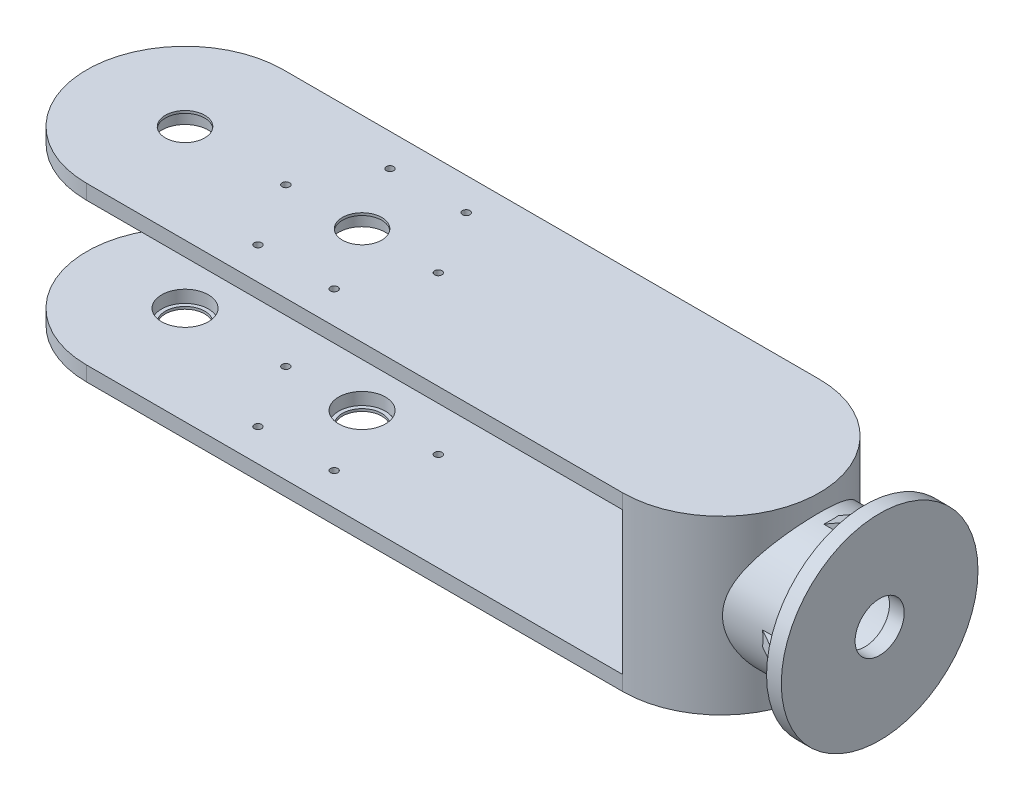
SolidWorks part; units mm, degrees
ref_plane "前视基准面" through (0, 0, 0) normal (0, 0, 1) x (1, 0, 0)
ref_plane "上视基准面" through (0, 0, 0) normal (0, 1, 0) x (1, 0, 0)
ref_plane "右视基准面" through (0, 0, 0) normal (1, 0, 0) x (0, 0, -1)
sketch "草图1" plane through (0, 0, 0) normal (0, 1, 0) x (1, 0, 0)
  line L1 (0, 40) -> (218, 40)
  line L4 (218, -40) -> (0, -40)
  arc A0 (0, 40) -> (0, -40) centre (0, 0) ccw
  arc A1 (218, -40) -> (218, 40) centre (218, 0) ccw
  dimension "D1" = 80
  dimension "D2" = 218
  dimension "D4" = 40
extrude "拉伸1" add sketch "草图1" along normal blind 3 and the other way blind 3
sketch "草图2" plane through (0, 3, 0) normal (0, 1, 0) x (-1, 0, 0)
  line L0 (-218, -31.8673) -> (-218, -40)
  line L1 (-218, 31.8673) -> (-218, 40)
  arc A0 (-218, 40) -> (-218, -40) centre (-218, 0) ccw
  arc A1 (-218, 31.8673) -> (-218, -31.8673) centre (-218, 0) ccw
extrude "拉伸2" add sketch "草图2" along normal blind 58
ref_plane "基准面1" through (282.5, 0, 0) normal (1, 0, 0) x (0, 0, -1)
sketch "草图3" plane through (282.5, 0, 0) normal (1, 0, 0) x (0, 0, -1)
  circle A0 centre (0, 32) radius 40
extrude "拉伸3" add sketch "草图3" along normal blind 0.0001 and the other way blind 6 separate body
sketch "草图4" plane through (0, 0, 0) normal (0, 0, 1) x (1, 0, 0)
  line L0 (282.5, 76.1494) -> (282.5, -15.8787)
  line L1 (282.5, -44) -> (282.5, 44) construction
  line L2 (282.5, -15.8787) -> (330.2143, 15.8142)
extrude "切除-拉伸1" cut sketch "草图4" against normal through all and the other way through all
sketch "草图5" plane through (276.5, 0, 0) normal (-1, 0, 0) x (0, 0, 1)
  circle A0 centre (0, 32) radius 28
  circle A1 centre (0, 32) radius 24
extrude "拉伸4" add sketch "草图5" along normal up to surface (29.9343 mm away) up to face at (231.3333, 20.3333, 0)
sketch "草图9" plane through (0, 0, 0) normal (0, 0, 1) x (1, 0, 0)
  line L0 (276.5, -3.6675) -> (263.0188, 4)
  line L1 (276.5, 72) -> (276.5, -8) construction
  line L2 (258, 4) -> (276.5, 4) construction
rib "筋5" sketch "草图9" sketch "草图9" thickness 6 extrusion direction parallel to sketch draft on no parameters "D1"=6
ref_axis "基准轴1" through (276.5, 32, 0) along (-1, 0, 0)
pattern_circular "阵列(圆周)1" count 4 every 90 about axis through (276.5, 32, 0) along (-1, 0, 0) of "筋5"
ref_plane "基准面2" through (0, 32, 0) normal (0, 1, 0) x (-1, 0, 0)
mirror "镜向1" about plane through (0, 32, 0) normal (0, 1, 0) of "拉伸1"
sketch "草图10" plane through (282.5, 0, 0) normal (1, 0, 0) x (0, 0, -1)
  line L0 (44, 32) -> (-44, 32) construction
  circle A0 centre (0, 32) radius 10
extrude "切除-拉伸2" cut sketch "草图10" against normal through all
sketch "草图11" plane through (0, 67, 0) normal (0, 1, 0) x (-1, 0, 0)
  circle A0 centre (0, 0) radius 8
extrude "切除-拉伸3" cut sketch "草图11" against normal through all
sketch "草图12" plane through (0, 67, 0) normal (0, 1, 0) x (-1, 0, 0)
  circle A0 centre (-72, 0) radius 8
  dimension "D1" = 72
extrude "切除-拉伸4" cut sketch "草图12" against normal through all
sketch "草图13" plane through (0, 3, 0) normal (0, 1, 0) x (-1, 0, 0)
  circle A0 centre (-72, 0) radius 9.5
  circle A1 centre (0, 0) radius 9.5
  dimension "D1" = 19
extrude "切除-拉伸5" cut sketch "草图13" against normal blind 5
mirror "镜向2" about plane through (0, 32, 0) normal (0, 1, 0) of "切除-拉伸5"
sketch "草图14" plane through (0, 67, 0) normal (0, 1, 0) x (-1, 0, 0)
  circle A1 centre (-41, 0) radius 1.5
  dimension "D2" = 3
extrude "切除-拉伸6" cut sketch "草图14" against normal through all
ref_axis "基准轴2" through (72, 66, 0) along (0, -1, 0)
pattern_circular "阵列(圆周)2" count 6 every 60 about axis through (72, 66, 0) along (0, -1, 0) of "切除-拉伸6"
